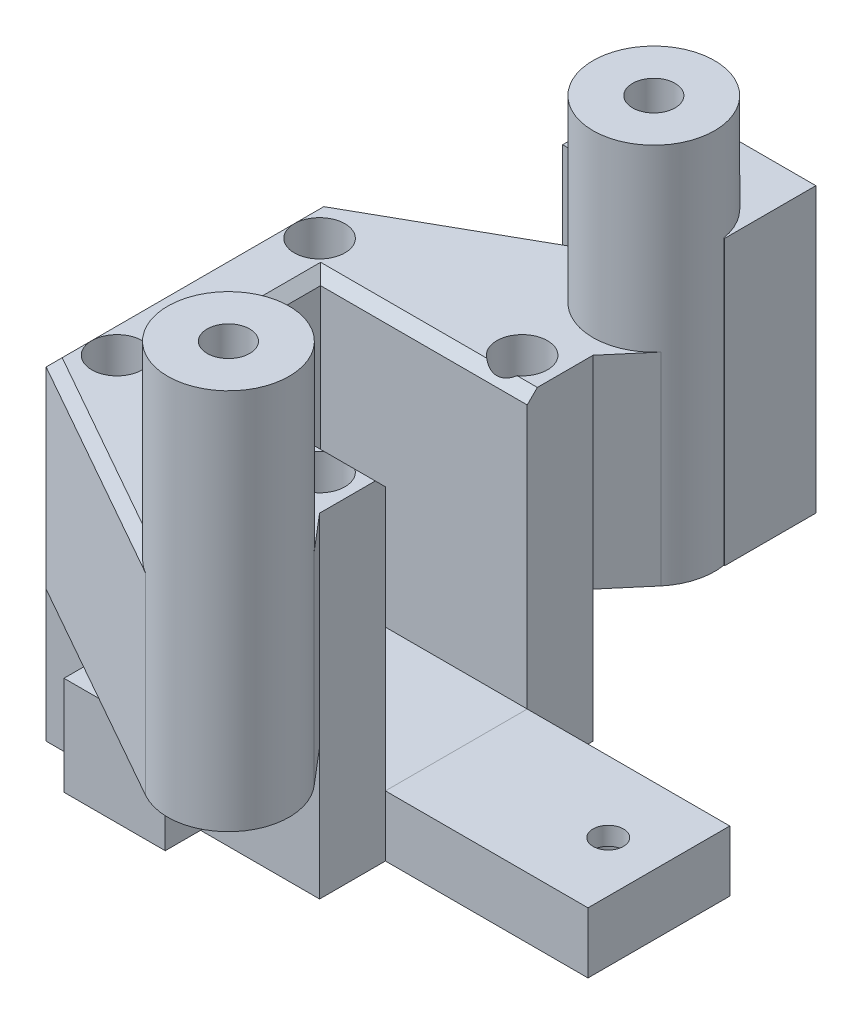
SolidWorks part; units mm, degrees
ref_plane "Front Plane" through (0, 0, 0) normal (0, 0, 1) x (1, 0, 0)
ref_plane "Top Plane" through (0, 0, 0) normal (0, 1, 0) x (1, 0, 0)
ref_plane "Right Plane" through (0, 0, 0) normal (1, 0, 0) x (0, 0, -1)
sketch "Sketch1" plane through (0, 0, 0) normal (0, 1, 0) x (1, 0, 0)
  line L0 (0, 13.5) -> (0, -13.5) construction
  line L5 (13.5, 13.5) -> (-13.5, 13.5)
  line L6 (13.5, 13.5) -> (13.5, -13.5)
  line L7 (13.5, -13.5) -> (-13.5, -13.5)
  line L8 (-13.5, 13.5) -> (-13.5, -13.5)
  line L9 (13.5, 0) -> (-13.5, 0) construction
  line L11 (-10, 10) -> (10, 10) construction
  line L12 (-10, 10) -> (-10, -10) construction
  line L13 (-10, -10) -> (10, -10) construction
  line L14 (10, 10) -> (10, -10) construction
  line L15 (-10, 10) -> (10, -10) construction
  line L16 (-10, -10) -> (10, 10) construction
  point P6 (0, 0)
  dimension "D1" = 27
  dimension "D2" = 27
  dimension "D3" = 20
  dimension "D4" = 20
extrude "Boss-Extrude1" add sketch "Sketch1" along normal blind 13
sketch "Sketch2" plane through (0, 13, 0) normal (0, 1, 0) x (1, 0, 0)
  line L0 (0, -13.5) -> (0, -25.9463) construction
  line L1 (-13.5, -13.5) -> (13.5, -13.5) construction
  line L2 (-13.5, 0) -> (-42.2961, 0) construction
  line L3 (-13.5, 13.5) -> (-13.5, -13.5) construction
  line L4 (13.5, -13.5) -> (13.5, 13.5) construction
  line L5 (-6.9, 7) -> (13.5, 7)
  line L6 (-6.9, 7) -> (-6.9, -7)
  line L7 (-6.9, -7) -> (13.5, -7)
  line L8 (13.5, 7) -> (13.5, -7)
  point P14 (-6.9, 0)
  dimension "D1" = 14
  dimension "D2" = 20.4
extrude "Cut-Extrude1" cut sketch "Sketch2" against normal blind 7
hole_wizard "Ø3.0mm Dowel Hole1" positions "Sketch3" profile "Sketch4" hole size "Ø3.0" standard "ANSI Metric"
sketch "Sketch3" plane through (0, 6, 0) normal (0, 1, 0) x (1, 0, 0)
  line L0 (3.5, 0) -> (13.5, 0) construction
  line L1 (13.5, -7) -> (13.5, 7) construction
  point P0 (3.5, 0)
  dimension "D1" = 10
sketch "Sketch4" plane through (3.5, 6, 0) normal (1, 0, 0) x (0, 0, 1)
  line L0 (0, 0) -> (0, 20.9013)
  line L1 (0, 20.9013) -> (1.5, 20)
  line L2 (1.5, 20) -> (1.5, 0)
  line L5 (1.5, 0) -> (0, 0)
  line L10 (0, 20.9013) -> (-1.5, 20) construction
  line L11 (0, -6.35) -> (0, 107.95) construction
  dimension "Hole Dia." = 3
  dimension "Hole Depth" = 20
  dimension "Drill Angle" = 118
sketch "Sketch5" plane through (0, 0, 0) normal (0, 1, 0) x (1, 0, 0)
  line L0 (-6.9, -7) -> (13.5, -7) construction
  line L1 (13.5, 7) -> (33.5, 7)
  line L2 (13.5, 7) -> (13.5, -7)
  line L3 (13.5, -7) -> (33.5, -7)
  line L4 (33.5, 7) -> (33.5, -7)
  dimension "D1" = 20
extrude "Boss-Extrude2" add sketch "Sketch5" along normal up to surface (6 mm away) separate body up to face at (3.5, 6, 1.5)
hole_wizard "Ø3.0mm Dowel Hole2" positions "Sketch6" profile "Sketch7" hole size "Ø3.0" standard "ANSI Metric"
sketch "Sketch6" plane through (0, 6, 0) normal (0, 1, 0) x (1, 0, 0)
  line L0 (3.5, 0) -> (28.5, 0) construction
  point P0 (28.5, 0)
  dimension "D1" = 25
sketch "Sketch7" plane through (28.5, 6, 0) normal (1, 0, 0) x (0, 0, 1)
  line L0 (0, 0) -> (0, 20.9013)
  line L1 (0, 20.9013) -> (1.5, 20)
  line L2 (1.5, 20) -> (1.5, 0)
  line L5 (1.5, 0) -> (0, 0)
  line L10 (0, 20.9013) -> (-1.5, 20) construction
  line L11 (0, -6.35) -> (0, 107.95) construction
  dimension "Hole Dia." = 3
  dimension "Hole Depth" = 20
  dimension "Drill Angle" = 118
hole_wizard "Ø3.0mm Dowel Hole3" positions "Sketch9" profile "Sketch10" hole size "Ø3.0" standard "ANSI Metric" end condition through all
sketch "Sketch9" plane through (0, 13, 0) normal (0, 1, 0) x (1, 0, 0)
  line L1 (10, -10) -> (-10, -10)
  line L2 (10, -10) -> (10, 10)
  line L3 (10, 10) -> (-10, 10)
  line L4 (-10, -10) -> (-10, 10)
  line L5 (0, -10) -> (0, 0) construction
  line L6 (0, 0) -> (-10, 0) construction
  point P0 (-10, 10)
  point P2 (-10, -10)
  point P9 (10, -10)
  point P10 (10, 10)
  dimension "D1" = 20
  dimension "D2" = 20
  dimension "D3" = 10
  dimension "D4" = 10
sketch "Sketch10" plane through (-10, 13, -10) normal (1, 0, 0) x (0, 0, 1)
  line L0 (0, 0) -> (0, 13)
  line L1 (0, 13) -> (1.5, 13)
  line L2 (1.5, 13) -> (1.5, 0)
  line L5 (1.5, 0) -> (0, 0)
  line L11 (0, -6.35) -> (0, 107.95) construction
  dimension "Thru Hole Dia." = 3
  dimension "Thru Hole Depth" = 13
sketch "Sketch11" plane through (0, 0, 0) normal (0, 1, 0) x (1, 0, 0)
  line L0 (14.5, 0) -> (14.5, 15) construction
  line L1 (13.5, -7) -> (13.5, 7) construction
  line L2 (0, 0) -> (12, 0) construction
  point P7 (12, 21)
  dimension "D1" = 1
  dimension "D2" = 15
  dimension "D3" = 12
  dimension "D4" = 6
sketch "Sketch12" plane through (0, 13, 0) normal (0, 1, 0) x (1, 0, 0)
  circle A0 centre (12, 21) radius 6
  dimension "D1" = 12
extrude "Boss-Extrude3" add sketch "Sketch12" along normal blind 37.7 separate body
sketch "Sketch13" plane through (0, 13, 0) normal (0, 1, 0) x (1, 0, 0)
  line L0 (13.5, 7) -> (13.5, 13.5)
  line L1 (13.5, 13.5) -> (16.5719, 17.1144)
  line L2 (9.0513, 26.2255) -> (-13.5, 13.5)
  line L6 (-13.5, 13.5) -> (-13.5, 0)
  line L7 (-13.5, 13.5) -> (-13.5, -13.5) construction
  line L8 (-13.5, 0) -> (-6.9, 0)
  line L9 (-6.9, 7) -> (-6.9, -7) construction
  line L10 (-6.9, 0) -> (-6.9, 7)
  line L11 (-6.9, 7) -> (13.5, 7)
  circle A1 centre (12, 21) radius 6 construction
  arc A2 (9.0513, 26.2255) -> (16.5719, 17.1144) centre (12, 21) ccw
  circle A3 centre (-10, 10) radius 2.5
  circle A4 centre (10, 10) radius 2.5
  dimension "D1" = 5
  dimension "D2" = 5
extrude "Boss-Extrude4" add sketch "Sketch13" along normal blind 20
pattern_linear "LPattern1" count 2 spacing 42 along (0, 0, 1) of "Boss-Extrude3"
mirror "Mirror5" about plane through (0, 0, 0) normal (0, 0, 1) of "Boss-Extrude4"
chamfer "Chamfer1" distance 1 angle 45 6 edges at (-2.2243, 33, -19.8627) (-13.5, 33, 0) (-2.2243, 33, 19.8627) (3.3, 33, 7) (3.3, 33, -7) (-6.9, 33, 0)
sketch "Sketch18" plane through (0, 0, 13.5) normal (0, 0, 1) x (1, 0, 0)
  line L0 (0, 0) -> (0, 5.75) construction
  line L1 (-5, 8.25) -> (-5, 13)
  line L2 (5, 3.25) -> (-5, 3.25)
  line L3 (5, 3.25) -> (5, 8.25)
  line L4 (5, 8.25) -> (-5, 8.25) construction
  line L5 (-5, 3.25) -> (-5, 8.25)
  line L6 (5, 3.25) -> (-5, 8.25) construction
  line L7 (5, 8.25) -> (-5, 3.25) construction
  line L8 (9.0513, 13) -> (-13.5, 13) construction
  line L9 (-5, 13) -> (5, 13)
  line L10 (5, 13) -> (5, 8.25)
  dimension "D1" = 5.75
  dimension "D2" = 5
  dimension "D3" = 10
extrude "Boss-Extrude5" add sketch "Sketch18" along normal blind 6.74
mirror "Mirror7" about plane through (0, 0, 0) normal (0, 0, 1) of "Boss-Extrude5"
hole_wizard "Hole1" positions "Sketch19" profile "Sketch20" legacy
sketch "Sketch19" plane through (0, 0, 0) normal (0, -1, 0) x (-1, 0, 0)
  point P0 (-3.5, 0)
  point P3 (-28.5, 0)
sketch "Sketch20" plane through (3.5, 0, 0) normal (1, 0, 0) x (0, 0, -1)
  line L0 (0, 0) -> (0, 4.2)
  line L1 (0, 4.2) -> (2.825, 4.2)
  line L2 (2.825, 4.2) -> (2.825, 0)
  line L3 (2.825, 0) -> (0, 0)
  line L4 (0, 110) -> (0, -10) construction
  dimension "Diameter" = 5.65
  dimension "Depth" = 4.2
ref_plane "Plane1" through (0, 0, -27) normal (0, 0, -1) x (-1, 0, 0)
sketch "Sketch21" plane through (0, 0, -27) normal (0, 0, -1) x (-1, 0, 0)
  line L0 (-18, 13) -> (-15, 13) construction
  line L1 (-18, 13) -> (-9.0513, 13) construction
  line L2 (-15, 13) -> (-15, 16) construction
  line L3 (-15, 16) -> (-5, 16) construction
  line L4 (-5, 16) -> (-5, 38) construction
  line L6 (-18, 13) -> (-2, 13)
  line L7 (-18, 13) -> (-18, 41)
  line L8 (-18, 41) -> (-2, 41)
  line L9 (-2, 13) -> (-2, 41)
  dimension "D1" = 3
  dimension "D2" = 3
  dimension "D3" = 10
  dimension "D4" = 22
  dimension "D5" = 16
  dimension "D6" = 28
extrude "Boss-Extrude7" add sketch "Sketch21" against normal blind 5
hole_wizard "M5x0.8 Tapped Hole2" positions "Sketch16" profile "Sketch17" tap size "M5x0.8" standard "ANSI Metric" end condition through all
sketch "Sketch16" plane through (0, 50.7, 0) normal (0, 1, 0) x (1, 0, 0)
  circle A0 centre (12, 21) radius 6 construction
  circle A1 centre (12, 21) radius 6 construction
  circle A2 centre (12, -21) radius 6 construction
  circle A3 centre (12, -21) radius 6 construction
  point P0 (12, 21)
  point P2 (12, -21)
sketch "Sketch17" plane through (12, 50.7, -21) normal (1, 0, 0) x (0, 0, 1)
  line L0 (0, 0) -> (0, 50.7)
  line L1 (0, 50.7) -> (2.1, 50.7)
  line L2 (2.1, 50.7) -> (2.1, 0)
  line L5 (2.1, 0) -> (0, 0)
  line L11 (0, -6.35) -> (0, 107.95) construction
  dimension "Thru Tap Drill Dia." = 4.2
  dimension "Thru Tap Drill Depth" = 50.7
cosmetic thread "Hole Thread2" parameters "D2"=5
cosmetic thread "Hole Thread3" parameters "D2"=5
sketch "Sketch22" plane through (0, 0, -27) normal (0, 0, -1) x (-1, 0, 0)
  line L5 (-2, 41) -> (-12, 41)
  line L6 (-12, 41) -> (-18, 41)
  line L7 (-18, 41) -> (-18, 13)
  line L8 (-18, 13) -> (-2, 13)
  line L9 (-2, 13) -> (-2, 41)
  line L10 (-2, 41) -> (-12, 41)
  line L11 (-12, 41) -> (-18, 41)
  line L12 (-18, 41) -> (-18, 13)
  line L13 (-18, 13) -> (-2, 13)
  line L14 (-2, 13) -> (-2, 41)
  dimension "D1" = 0
extrude "Boss-Extrude8" add sketch "Sketch22" along normal blind 4
hole_wizard "3/32 (0.140625) Dowel Hole1" positions "Sketch24" profile "Sketch25" hole size "3/32" standard "ANSI Inch"
sketch "Sketch24" plane through (0, 0, -31) normal (0, 0, -1) x (-1, 0, 0)
  line L0 (-15, 16) -> (-5, 16) construction
  line L1 (-5, 16) -> (-5, 38) construction
  line L3 (-18, 13) -> (-2, 13) construction
  line L4 (-18, 41) -> (-18, 13) construction
  point P0 (-15, 16)
  point P2 (-5, 38)
  point P11 (-15.7107, 16.3519)
  dimension "D1" = 10
  dimension "D2" = 22
  dimension "D3" = 3
  dimension "D4" = 3
sketch "Sketch25" plane through (15, 16, -31) normal (1, 0, 0) x (0, 1, 0)
  line L0 (0, 0) -> (0, 10.0731)
  line L1 (0, 10.0731) -> (1.7859, 9)
  line L2 (1.7859, 9) -> (1.7859, 0)
  line L5 (1.7859, 0) -> (0, 0)
  line L10 (0, 10.0731) -> (-1.7859, 9) construction
  line L11 (0, -6.35) -> (0, 107.95) construction
  dimension "Hole Dia." = 3.5719
  dimension "Hole Depth" = 9
  dimension "Drill Angle" = 118
